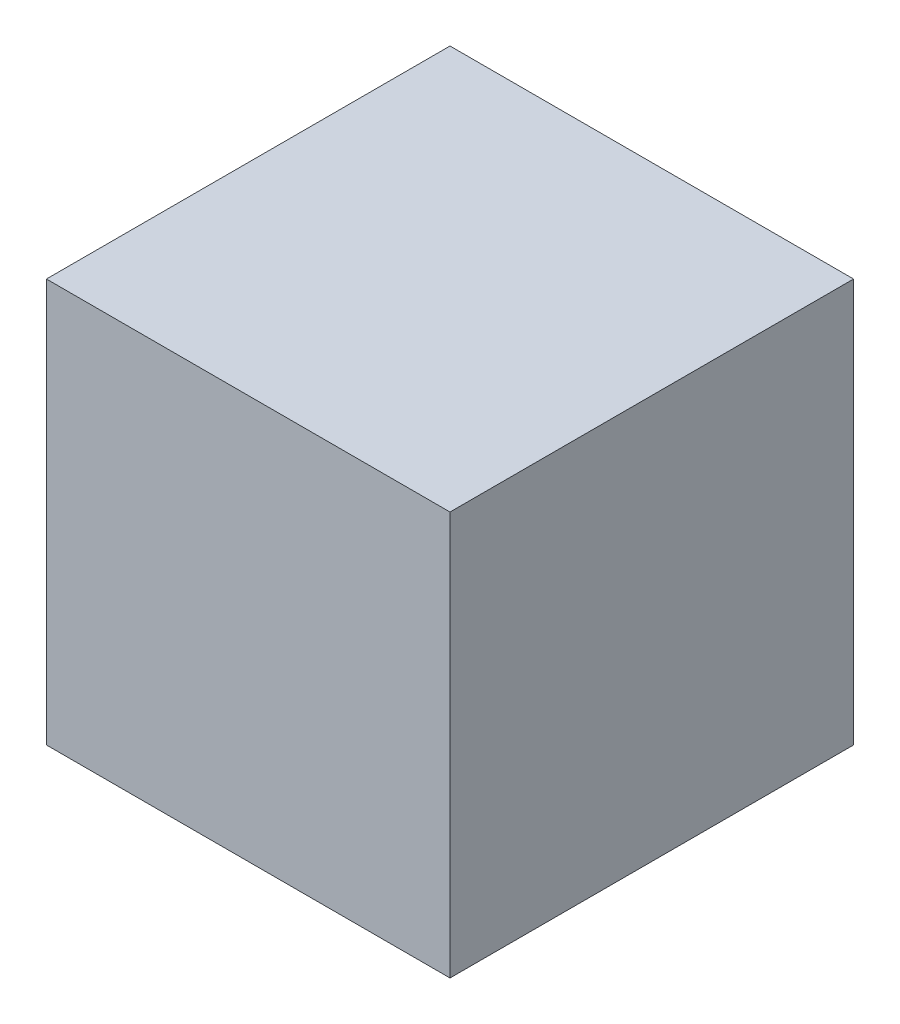
SolidWorks part; units mm, degrees
ref_plane "Front Plane" through (0, 0, 0) normal (0, 0, 1) x (1, 0, 0)
ref_plane "Top Plane" through (0, 0, 0) normal (0, 1, 0) x (1, 0, 0)
ref_plane "Right Plane" through (0, 0, 0) normal (1, 0, 0) x (0, 0, -1)
sketch "Sketch1" plane through (0, 0, 0) normal (0, 1, 0) x (1, 0, 0)
  line L1 (-114.3, -101.6) -> (88.9, -101.6)
  line L2 (-114.3, -101.6) -> (-114.3, 101.6)
  line L3 (-114.3, 101.6) -> (88.9, 101.6)
  line L4 (88.9, -101.6) -> (88.9, 101.6)
  line L5 (-114.3, -101.6) -> (88.9, 101.6) construction
  line L6 (-114.3, 101.6) -> (88.9, -101.6) construction
  point P0 (-12.7, 0)
  dimension "D1" = 203.2
  dimension "D2" = 203.2
  dimension "D3" = 12.7
extrude "Boss-Extrude1" add sketch "Sketch1" along normal blind 203.2
sketch "Sketch2" plane through (0, 0, 0) normal (0, 1, 0) x (1, 0, 0)
  line L1 (-46.482, -38.9001) -> (46.482, -38.9001)
  line L2 (-46.482, -38.9001) -> (-46.482, 38.9001)
  line L3 (-46.482, 38.9001) -> (46.482, 38.9001)
  line L4 (46.482, -38.9001) -> (46.482, 38.9001)
  line L5 (-46.482, -38.9001) -> (46.482, 38.9001) construction
  line L6 (-46.482, 38.9001) -> (46.482, -38.9001) construction
  point P0 (0, 0)
  dimension "D1" = 92.964
  dimension "D2" = 77.8002
extrude "Boss-Extrude2" add sketch "Sketch2" along normal blind 20.32 separate body
sketch "Boat Sketch" plane through (0, 0, 0) normal (0, 0, 1) x (1, 0, 0)
  line L0 (-114.3, 0) -> (88.9, 0) construction
  line L2 (-46.482, 0) -> (46.482, 0) construction
  line L3 (-46.482, 20.32) -> (46.482, 20.32) construction
  arc A0 (46.482, 0) -> (56.0914, 11.5009) centre (59.1552, -0.8239) cw
  arc A1 (56.0914, 11.5009) -> (71.882, 25.4) centre (50.5765, 33.6857) ccw
  arc A2 (56.0914, 11.5009) -> (-54.102, 6.35) centre (-11.9132, 285.0613) cw
  arc A3 (-46.482, 0) -> (-54.102, 6.35) centre (-57.7768, -5.8067) ccw
  arc A4 (-54.102, 6.35) -> (-66.802, 28.575) centre (-103.1359, -6.9283) ccw
  arc A5 (-66.802, 28.575) -> (-54.102, 27.5646) centre (-77.5674, -187.0564) cw
  arc A6 (-54.102, 27.5646) -> (71.882, 25.4) centre (20.6566, 711.327) ccw
  dimension "D3" = 22.86
  dimension "D6" = 12.7
  dimension "D11" = 50.8
  dimension "D12" = 215.9
  dimension "D1" = 25.4
  dimension "D2" = 25.4
  dimension "D4" = 7.62
  dimension "D5" = 6.35
  dimension "D7" = 3.175
  dimension "D8" = 28.575
  dimension "D9" = 3.1699
  dimension "D10" = 20.32
sketch "Balloon Sketch" plane through (0, 0, 0) normal (0, 0, 1) x (1, 0, 0)
  line L0 (-72.295, 139.7) -> (49927.705, 139.7) construction
  line L1 (0, 0) -> (0, 50000) construction
  line L2 (-19.05, 198.12) -> (19.05, 198.12) construction
  line L3 (-69.85, 117.5813) -> (-69.85, 179.9578) construction
  line L4 (-69.85, 117.5813) -> (-91.6467, 146.7913)
  line L6 (-114.3, 203.2) -> (-114.3, 0) construction
  arc A0 (76.1755, 152.0409) -> (-76.1755, 152.0409) centre (0, 109.6962) ccw
  arc A1 (-76.1755, 127.3591) -> (76.1755, 127.3591) centre (0, 169.7037) ccw
  arc A2 (-76.1755, 152.0409) -> (-76.1755, 127.3591) centre (-53.975, 139.7) ccw
  arc A3 (76.1755, 152.0409) -> (76.1755, 127.3591) centre (53.975, 139.7) cw
  arc A4 (-34.925, 89.8538) -> (-19.05, 63.5) centre (-68.4593, 51.695) cw
  arc A5 (-19.05, 198.12) -> (19.05, 198.12) centre (0, 137.5449) cw
  arc A6 (-91.6467, 146.7913) -> (-57.15, 175.4964) centre (-17.28, 92.5012) cw
  arc A7 (-69.85, 117.5813) -> (-88.392, 125.9633) centre (-96.407, 83.5336) ccw
  arc A8 (-88.392, 125.9633) -> (-114.3, 146.7913) centre (-125.0176, 106.932) ccw
  arc A9 (-114.3, 146.7913) -> (-57.15, 175.4964) centre (-36.4711, 63.0825) cw
  point P10 (0, 82.55)
  point P14 (-81.8263, 139.7)
  point P17 (81.8263, 139.7)
  point P22 (0, 201.0449)
  dimension "D2" = 25.4
  dimension "D3" = 158.75
  dimension "D4" = 114.3
  dimension "D7" = 38.1
  dimension "D11" = 63.5
  dimension "D13" = 18.542
  dimension "D15" = 43.18
  dimension "D17" = 41.275
  dimension "D18" = 92.075
  dimension "D19" = 114.3
  dimension "D8" = 50.8
  dimension "D1" = 139.7
  dimension "D5" = 69.85
  dimension "D6" = 63.5
  dimension "D9" = 38.1
  dimension "D10" = 58.42
  dimension "D12" = 69.85
  dimension "D14" = 8.382
  dimension "D16" = 29.21
  dimension "D20" = 12.7
sketch "Engine Sketch" plane through (0, 0, 0) normal (0, 0, 1) x (1, 0, 0)
  line L0 (-6.35, 71.12) -> (-6.35, 45.72)
  line L1 (-6.35, 45.72) -> (-15.875, 45.72)
  line L2 (-15.875, 45.72) -> (-25.4071, 29.21)
  line L3 (-25.4071, 29.21) -> (-57.1571, 29.21)
  line L4 (6.35, 71.12) -> (6.35, 45.72)
  line L5 (6.35, 45.72) -> (15.875, 45.72)
  line L6 (15.875, 45.72) -> (22.225, 34.7215)
  line L7 (22.225, 34.7215) -> (22.225, 22.86)
  line L8 (-57.1571, 29.21) -> (-57.1571, 22.86)
  line L9 (0, 0) -> (0, 50000) construction
  line L11 (-114.3, 0) -> (88.9, 0) construction
  dimension "D1" = 12.7
  dimension "D2" = 9.525
  dimension "D3" = 22.86
  dimension "D4" = 60
  dimension "D5" = 60
  dimension "D6" = 45.72
  dimension "D7" = 25.4
  dimension "D8" = 22.225
  dimension "D9" = 6.35
  dimension "D10" = 31.75
